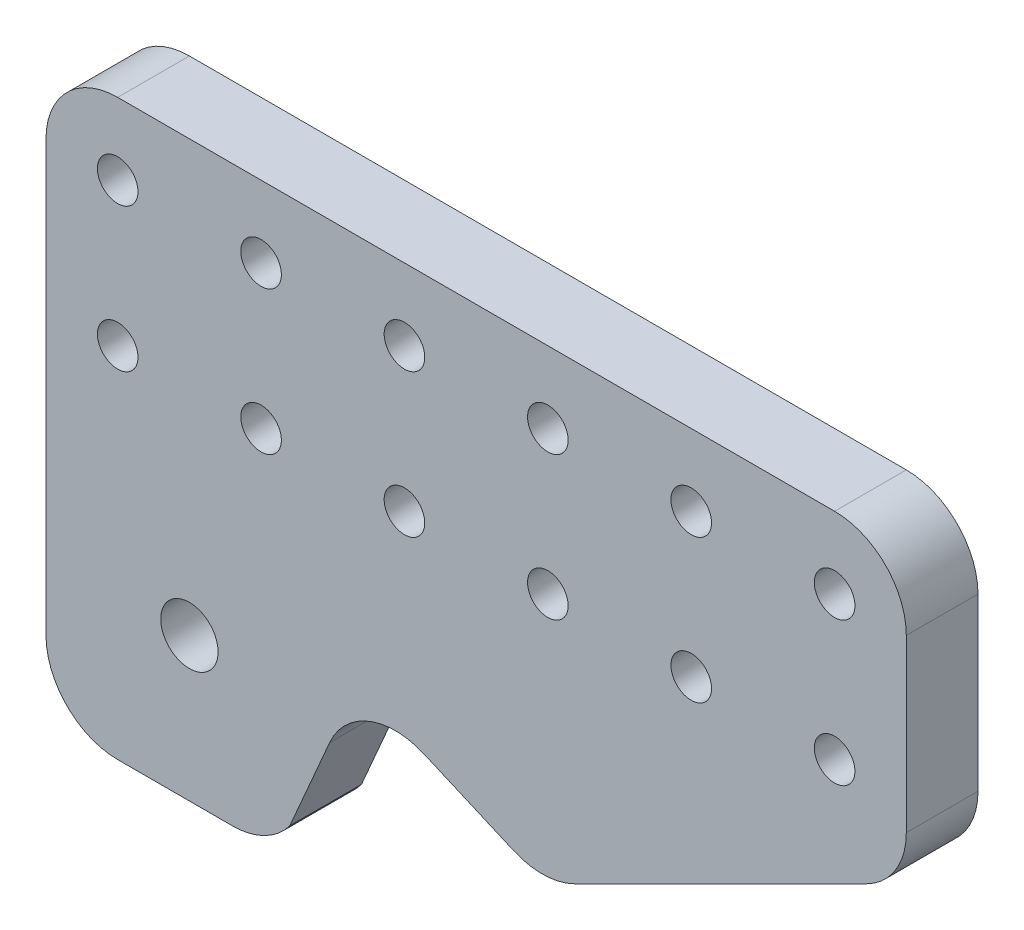
SolidWorks part; units mm, degrees
ref_plane "Front Plane" through (0, 0, 0) normal (0, 0, 1) x (1, 0, 0)
ref_plane "Top Plane" through (0, 0, 0) normal (0, 1, 0) x (1, 0, 0)
ref_plane "Right Plane" through (0, 0, 0) normal (1, 0, 0) x (0, 0, -1)
sketch "Sketch1" plane through (0, 0, 0) normal (0, 0, 1) x (1, 0, 0)
  line L0 (25.4, 0) -> (76.2, 25.4)
  line L3 (0, 50.8) -> (76.2, 50.8)
  line L4 (76.2, 25.4) -> (76.2, 50.8)
  line L7 (0, 0) -> (25.4, 0)
  line L9 (0, 50.8) -> (0, 0)
  circle A0 centre (12.7, 12.7) radius 2.54
  circle A1 centre (69.85, 44.45) radius 1.7977
  circle A2 centre (57.15, 44.45) radius 1.7977
  circle A3 centre (44.45, 44.45) radius 1.7977
  circle A4 centre (31.75, 44.45) radius 1.7977
  circle A5 centre (19.05, 44.45) radius 1.7977
  circle A6 centre (6.35, 44.45) radius 1.7977
  circle A7 centre (57.15, 31.75) radius 1.7977
  circle A8 centre (44.45, 31.75) radius 1.7977
  circle A9 centre (31.75, 31.75) radius 1.7977
  circle A10 centre (19.05, 31.75) radius 1.7977
  circle A11 centre (6.35, 31.75) radius 1.7977
  circle A12 centre (69.85, 31.75) radius 1.7977
  point P8 (12.7, 0)
  dimension "D6" = 5.08
  dimension "D2" = 25.4
  dimension "D3" = 25.4
  dimension "D4" = 76.2
  dimension "D5" = 38.1
  dimension "D7" = 6.35
  dimension "D8" = 6.35
  dimension "D11" = 12.7
  dimension "D9" = 6
  dimension "D10" = 2
extrude "Boss-Extrude1" add sketch "Sketch1" along normal blind 6.35
sketch "Sketch2" plane through (0, 0, 6.35) normal (0, 0, 1) x (1, 0, 0)
  line L0 (21.59, 0) -> (21.59, 2.54)
  line L1 (0, 0) -> (25.4, 0) construction
  line L2 (21.59, 2.54) -> (27.6511, 16.5229)
  line L3 (27.6511, 16.5229) -> (44.1459, 9.373)
  line L4 (25.4, 0) -> (76.2, 25.4) construction
  line L5 (21.59, 0) -> (25.4, 0)
  line L6 (25.4, 0) -> (44.1459, 9.373)
  dimension "D1" = 130
  dimension "D2" = 3.81
  dimension "D3" = 2.54
  dimension "D4" = 15.24
extrude "Cut-Extrude1" cut sketch "Sketch2" against normal through all
fillet "Fillet1" radius 6.35 7 edges at (27.6511, 16.5229, 3.175) (44.1459, 9.373, 3.175) (76.2, 25.4, 3.175) (76.2, 50.8, 3.175) (0, 50.8, 3.175) (0, 0, 3.175) (21.59, 0, 3.175)
